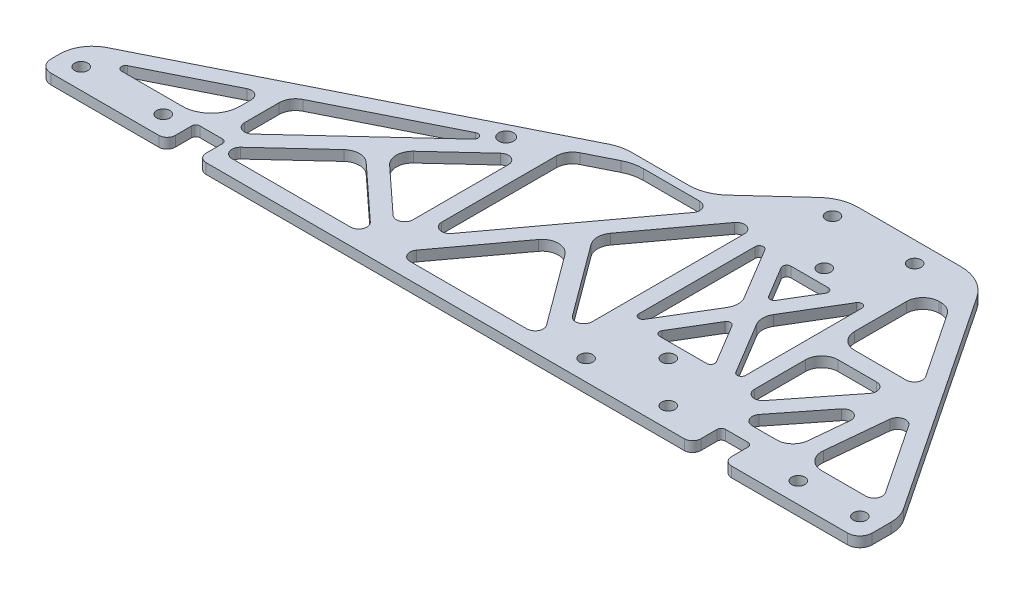
SolidWorks part; units mm, degrees
ref_plane "Front Plane" through (0, 0, 0) normal (0, 0, 1) x (1, 0, 0)
ref_plane "Top Plane" through (0, 0, 0) normal (0, 1, 0) x (1, 0, 0)
ref_plane "Right Plane" through (0, 0, 0) normal (1, 0, 0) x (0, 0, -1)
sketch "Sketch1" plane through (0, 0, 0) normal (0, 1, 0) x (1, 0, 0)
  line L0 (0, 0) -> (254, 0)
  line L2 (203.2, 88.9) -> (152.4, 88.9)
  line L4 (0, 0) -> (0, 12.7)
  line L5 (0, 12.7) -> (152.4, 88.9)
  line L6 (203.2, 88.9) -> (254, 12.7)
  line L7 (254, 12.7) -> (254, 0)
  line L8 (0, 6.35) -> (44.45, 6.35) construction
  line L9 (254, 6.35) -> (228.6, 6.35) construction
  line L10 (139.7, 82.55) -> (207.4333, 82.55) construction
  line L11 (44.45, 0) -> (44.45, 34.925) construction
  line L12 (156.6333, 12.7) -> (154.0933, 7.62)
  line L13 (224.7006, 47.4909) -> (221.314, 12.7) construction
  line L20 (127, 76.2) -> (211.6667, 76.2)
  line L21 (154.0933, 76.2) -> (101.6, 5.08) construction
  line L22 (154.0933, 12.7) -> (154.0933, 7.62)
  line L23 (247.8946, 12.7) -> (194.7333, 12.7)
  line L24 (224.7006, 47.4909) -> (197.2733, 12.7) construction
  line L28 (224.7006, 47.4909) -> (194.7333, 47.4909) construction
  line L31 (5.08, 9.5604) -> (153.5992, 83.82)
  line L32 (200.4813, 83.82) -> (153.5992, 83.82)
  line L33 (200.4813, 83.82) -> (248.92, 11.1619)
  line L34 (248.92, 11.1619) -> (248.92, 5.08)
  line L35 (5.08, 5.08) -> (248.92, 5.08)
  line L36 (5.08, 5.08) -> (5.08, 9.5604)
  line L37 (101.6, 5.08) -> (101.6, 57.8204) construction
  line L39 (127.8467, 40.64) -> (154.0933, 5.08) construction
  line L40 (101.6, 57.8204) -> (44.45, 5.08) construction
  line L41 (73.025, 31.4502) -> (101.6, 5.08) construction
  line L42 (154.0933, 7.62) -> (154.0933, 5.08)
  line L83 (152.8233, 5.08) -> (150.2833, 0)
  line L84 (125.803, 39.1316) -> (152.0497, 3.5716)
  line L107 (152.0497, 77.7084) -> (99.5564, 6.5884)
  line L108 (156.6333, 76.2) -> (194.7333, 12.7) construction
  line L113 (194.7333, 76.2) -> (156.6333, 12.7) construction
  line L117 (104.14, 5.08) -> (104.14, 63.6207)
  line L118 (156.6333, 12.7) -> (194.7333, 12.7)
  line L119 (194.7333, 12.7) -> (201.0833, 0)
  line L120 (154.0933, 6.35) -> (197.9083, 6.35) construction
  line L126 (192.5553, 77.5068) -> (154.4553, 14.0068)
  line L127 (154.4553, 74.8932) -> (192.5553, 11.3932)
  line L128 (156.6333, 12.7) -> (156.6333, 76.2) construction
  line L129 (194.7333, 12.7) -> (194.7333, 76.2) construction
  line L130 (197.2733, 12.7) -> (197.2733, 76.2)
  line L131 (159.1733, 12.7) -> (159.1733, 76.2)
  line L132 (192.1933, 12.7) -> (192.1933, 76.2)
  line L133 (154.0933, 12.7) -> (154.0933, 76.2)
  line L147 (196.9114, 74.8932) -> (158.8114, 11.3932)
  line L148 (158.8114, 77.5068) -> (196.9114, 14.0068)
  line L154 (104.14, 63.6207) -> (42.7274, 6.9466)
  line L155 (71.3024, 29.5836) -> (99.8774, 3.2134)
  line L156 (224.7006, 50.0309) -> (194.7333, 50.0309)
  line L157 (222.7059, 49.0635) -> (195.2786, 14.2725)
  line L158 (197.2733, 12.7) -> (197.2733, 7.62)
  line L159 (222.1726, 47.737) -> (218.7859, 12.9461)
  line L160 (129.8903, 42.1484) -> (156.137, 6.5884)
  line L163 (156.137, 74.6916) -> (103.6436, 3.5716)
  line L164 (99.06, 5.08) -> (99.06, 52.0201)
  line L165 (99.06, 52.0201) -> (46.1726, 3.2134)
  line L166 (175.6833, 19.05) -> (162.9833, 6.35) construction
  line L167 (175.6833, 19.05) -> (188.3833, 6.35) construction
  line L168 (162.9833, 82.55) -> (175.6833, 67.31) construction
  line L169 (175.6833, 67.31) -> (188.3833, 82.55) construction
  line L170 (161.6625, 21.082) -> (189.7041, 21.082) construction
  line L171 (161.6625, 23.622) -> (189.7041, 23.622)
  line L172 (163.1865, 65.278) -> (188.1801, 65.278) construction
  line L173 (163.1865, 62.738) -> (188.1801, 62.738)
  line L174 (74.7476, 33.3168) -> (103.3226, 6.9466)
  line L175 (224.7006, 44.9509) -> (194.7333, 44.9509)
  line L176 (226.6953, 45.9184) -> (199.268, 11.1275)
  line L177 (227.2287, 47.2449) -> (223.842, 12.4539)
  line L178 (8.8192, 11.43) -> (44.45, 11.43)
  line L179 (46.99, 0) -> (46.99, 34.925)
  line L180 (41.91, 0) -> (41.91, 34.925)
  line L181 (198.2745, 13.97) -> (221.4376, 13.97)
  line L182 (118.0392, 66.04) -> (146.5943, 66.04)
  circle A0 centre (6.7733, 6.35) radius 2.032
  circle A1 centre (32.1733, 6.35) radius 2.032
  circle A2 centre (228.6, 6.35) radius 2.032
  circle A3 centre (247.65, 6.35) radius 2.032
  circle A4 centre (162.9833, 82.55) radius 2.032
  circle A5 centre (188.3833, 82.55) radius 2.032
  circle A28 centre (162.9833, 6.35) radius 2.032
  circle A29 centre (188.3833, 6.35) radius 2.032
  arc A32 (197.2733, 12.7) -> (192.1933, 12.7) centre (194.7333, 12.7) cw
  arc A33 (197.2733, 76.2) -> (192.1933, 76.2) centre (194.7333, 76.2) ccw
  arc A34 (159.1733, 12.7) -> (154.0933, 12.7) centre (156.6333, 12.7) cw
  arc A35 (159.1733, 76.2) -> (154.0933, 76.2) centre (156.6333, 76.2) ccw
  arc A45 (192.5553, 77.5068) -> (196.9114, 74.8932) centre (194.7333, 76.2) cw
  arc A46 (154.4553, 14.0068) -> (158.8114, 11.3932) centre (156.6333, 12.7) ccw
  arc A47 (154.4553, 74.8932) -> (158.8114, 77.5068) centre (156.6333, 76.2) cw
  arc A48 (192.5553, 11.3932) -> (196.9114, 14.0068) centre (194.7333, 12.7) ccw
  circle A59 centre (175.6833, 19.05) radius 2.032
  circle A60 centre (175.6833, 67.31) radius 2.032
  arc A61 (125.803, 39.1316) -> (129.8903, 42.1484) centre (127.8467, 40.64) cw
  arc A62 (152.0497, 3.5716) -> (156.137, 6.5884) centre (154.0933, 5.08) ccw
  arc A63 (152.0497, 77.7084) -> (156.137, 74.6916) centre (154.0933, 76.2) cw
  arc A64 (99.5564, 6.5884) -> (103.6436, 3.5716) centre (101.6, 5.08) ccw
  arc A65 (104.14, 5.08) -> (99.06, 5.08) centre (101.6, 5.08) cw
  arc A66 (42.7274, 6.9466) -> (46.1726, 3.2134) centre (44.45, 5.08) ccw
  arc A67 (71.3024, 29.5836) -> (74.7476, 33.3168) centre (73.025, 31.4502) cw
  arc A68 (99.8774, 3.2134) -> (103.3226, 6.9466) centre (101.6, 5.08) ccw
  arc A69 (224.7006, 50.0309) -> (224.7006, 44.9509) centre (224.7006, 47.4909) cw
  arc A70 (194.7333, 50.0309) -> (194.7333, 44.9509) centre (194.7333, 47.4909) ccw
  arc A71 (222.7059, 49.0635) -> (226.6953, 45.9184) centre (224.7006, 47.4909) cw
  arc A72 (195.2786, 14.2725) -> (199.268, 11.1275) centre (197.2733, 12.7) ccw
  arc A73 (222.1726, 47.737) -> (227.2287, 47.2449) centre (224.7006, 47.4909) cw
  arc A74 (218.7859, 12.9461) -> (223.842, 12.4539) centre (221.314, 12.7) ccw
  arc A75 (46.99, 0) -> (41.91, 0) centre (44.45, 0) cw
  arc A76 (46.99, 34.925) -> (41.91, 34.925) centre (44.45, 34.925) ccw
  dimension "D7" = 4.064
  dimension "D8" = 25.4
  dimension "D9" = 130.81
  dimension "D10" = 19.05
  dimension "D11" = 6.35
  dimension "D13" = 19.05
  dimension "D1" = 254
  dimension "D2" = 50.8
  dimension "D3" = 88.9
  dimension "D4" = 152.4
  dimension "D5" = 12.7
  dimension "D6" = 6.35
  dimension "D12" = 25.4
  dimension "D14" = 44.45
  dimension "D15" = 12.7
  dimension "D16" = 57.15
  dimension "D18" = 12.7
  dimension "D19" = 2.54
  dimension "D20" = 50.8
  dimension "D21" = 25.4
  dimension "D22" = 2.54
  dimension "D23" = 6.35
  dimension "D24" = 2.54
  dimension "D29" = 6.35
  dimension "D30" = 38.1
  dimension "D31" = 25.4
  dimension "D32" = 6.35
  dimension "D33" = 2.54
  dimension "D36" = 12.7
  dimension "D38" = 15.24
  dimension "D39" = 2.54
  dimension "D40" = 2.54
  dimension "D27" = 1.27
  dimension "D28" = 17.78
  dimension "D17" = 5.08
  dimension "D25" = 2.54
  dimension "D26" = 2.54
  dimension "D37" = 2.54
extrude "Boss-Extrude1" add sketch "Sketch1" along normal blind 3.175 contours L0 L7 L6 L2 L5 L4 | A0 | A1 | A5 | A4 | A2 | A3
extrude "Cut-Extrude2" cut sketch "Sketch1<3>" along normal through all contours L154 L31 L11 | L155 L165 L35 | L165 L174 L164 | L117 L107 L20 L31 | L84 L163 L35 | L133 L163 L160 L22 | L157 L175 L130 | L156 L33 L20 L130 | L147 L148 L132 | L131 L126 L127 | L173 L148 L126 | L147 L171 L127 | L33 L177 L23 | L178 L180 L31 | L176 L181 L159 | A28 | A59 | A29 | A60 region at (30.8797, 0, -16.9451) region at (73.025, 0, -12.718) region at (62.4687, 0, -31.7097) region at (127.8467, 0, -15.5076) region at (91.6301, 0, -31.4502) region at (117.6489, 0, -47.5459) region at (206.5243, 0, -60.8789) region at (146.3968, 0, -40.64) region at (204.6702, 0, -35.5682) region at (175.6833, 0, -28.919) region at (187.6774, 0, -44.45) region at (213.9093, 0, -22.3524) region at (163.6893, 0, -44.45) region at (232.896, 0, -23.1836) region at (175.6833, 0, -58.2876)
sketch "Sketch1<3>" plane through (0, 0, 0) normal (0, 1, 0) x (1, 0, 0) same geometry as "Sketch1"
fillet "Fillet1" radius 3.81 2 edges at (254, 1.5875, 0) (0, 1.5875, 0)
fillet "Fillet2" radius 10.16 2 edges at (254, 1.5875, -12.7) (0, 1.5875, -12.7)
fillet "Fillet3" radius 12.7 2 edges at (203.2, 1.5875, -88.9) (152.4, 1.5875, -88.9)
fillet "Fillet4" radius 1.27 12 edges at (159.1733, 1.5875, -67.0298) (192.1933, 1.5875, -67.0298) (192.1933, 1.5875, -21.8702) (159.1733, 1.5875, -21.8702) (183.694, 1.5875, -62.738) (167.6727, 1.5875, -62.738) (175.6833, 1.5875, -49.3869) (185.218, 1.5875, -23.622) (166.1487, 1.5875, -23.622) (175.6833, 1.5875, -39.5131) (93.426, 1.5875, -53.7334) (8.8192, 1.5875, -11.43)
fillet "Fillet5" radius 2.54 19 edges at (223.0073, 1.5875, -50.0309) (247.8946, 1.5875, -12.7) (226.9275, 1.5875, -44.1507) (221.3335, 1.5875, -39.1171) (197.2733, 1.5875, -16.8027) (219.4639, 1.5875, -44.9509) (104.14, 1.5875, -12.7984) (99.06, 1.5875, -52.0201) (48.1953, 1.5875, -5.08) (97.8547, 1.5875, -5.08) (99.06, 1.5875, -10.8803) (104.7569, 1.5875, -5.08) (150.9364, 1.5875, -5.08) (154.0933, 1.5875, -9.3572) (154.0933, 1.5875, -71.9228) (41.91, 1.5875, -27.9754) (46.99, 1.5875, -10.8803) (201.5089, 1.5875, -13.97) (143.4373, 1.5875, -66.04)
fillet "Fillet6" radius 5.08 14 edges at (172.7212, 1.5875, -44.45) (178.6455, 1.5875, -44.45) (223.866, 1.5875, -12.7) (197.2733, 1.5875, -50.0309) (197.2733, 1.5875, -44.9509) (197.2733, 1.5875, -76.2) (205.5613, 1.5875, -76.2) (73.025, 1.5875, -27.9939) (76.7703, 1.5875, -31.4502) (104.14, 1.5875, -59.0904) (131.0036, 1.5875, -40.64) (127.8467, 1.5875, -36.3628) (46.99, 1.5875, -30.5154) (218.8856, 1.5875, -13.97)
fillet "Fillet7" radius 12.7 1 edges at (118.0392, 1.5875, -66.04)
fillet "Fillet10" radius 8.89 1 edges at (41.91, 1.5875, -11.43)
sketch "Sketch4" plane through (0, 3.175, 0) normal (0, 1, 0) x (1, 0, 0)
  line L0 (121.0373, 66.04) -> (138.4056, 66.04) construction
  line L1 (121.0373, 66.04) -> (138.4056, 66.04)
  line L2 (121.0373, 68.58) -> (113.3689, 68.58) construction
  line L4 (138.4056, 66.04) -> (163.3832, 88.9)
  line L5 (121.0373, 68.58) -> (111.76, 68.58)
  line L6 (252.2936, 15.2596) -> (206.9702, 83.2447)
  line L7 (196.4032, 88.9) -> (155.3981, 88.9)
  line L8 (149.7185, 87.5592) -> (5.6163, 15.5082)
  line L9 (0, 6.4208) -> (0, 3.81)
  line L10 (3.81, 0) -> (250.19, 0)
  line L11 (254, 3.81) -> (254, 9.6238)
  line L12 (252.2936, 15.2596) -> (206.9702, 83.2447)
  line L13 (196.4032, 88.9) -> (155.3981, 88.9)
  line L14 (149.7185, 87.5592) -> (5.6163, 15.5082)
  line L15 (0, 6.4208) -> (0, 3.81)
  line L16 (3.81, 0) -> (250.19, 0)
  line L17 (254, 3.81) -> (254, 9.6238)
  line L18 (121.0373, 68.58) -> (137.4188, 68.58)
  line L19 (137.4188, 68.58) -> (159.621, 88.9)
  line L20 (138.4056, 66.04) -> (155.3658, 81.5624) construction
  line L21 (196.4032, 88.9) -> (155.3981, 88.9) construction
  line L22 (137.4188, 68.58) -> (153.651, 83.4361) construction
  line L23 (5.6163, 15.5082) -> (149.7185, 87.5592) construction
  line L29 (121.0373, 66.04) -> (113.3689, 66.04) construction
  arc A6 (206.9702, 83.2447) -> (196.4032, 88.9) centre (196.4032, 76.2) ccw
  arc A7 (155.3981, 88.9) -> (149.7185, 87.5592) centre (155.3981, 76.2) ccw
  arc A8 (5.6163, 15.5082) -> (0, 6.4208) centre (10.16, 6.4208) ccw
  arc A9 (0, 3.81) -> (3.81, 0) centre (3.81, 3.81) ccw
  arc A10 (250.19, 0) -> (254, 3.81) centre (250.19, 3.81) ccw
  arc A11 (254, 9.6238) -> (252.2936, 15.2596) centre (243.84, 9.6238) ccw
  arc A12 (206.9702, 83.2447) -> (196.4032, 88.9) centre (196.4032, 76.2) ccw
  arc A13 (155.3981, 88.9) -> (149.7185, 87.5592) centre (155.3981, 76.2) ccw
  arc A14 (5.6163, 15.5082) -> (0, 6.4208) centre (10.16, 6.4208) ccw
  arc A15 (0, 3.81) -> (3.81, 0) centre (3.81, 3.81) ccw
  arc A16 (250.19, 0) -> (254, 3.81) centre (250.19, 3.81) ccw
  arc A17 (254, 9.6238) -> (252.2936, 15.2596) centre (243.84, 9.6238) ccw
  point P18 (111.76, 68.58)
  point P28 (163.223, 94.3115)
  point P30 (164.7518, 88.9)
  point P33 (159.7969, 88.9)
  dimension "D2" = 2.54
  dimension "D4" = 33.02
  dimension "D1" = 0
extrude "Cut-Extrude5" cut sketch "Sketch4" against normal through all and the other way through all contours L13 A13 L14 L5 L18 L19 region at (137.3323, 3.175, -76.8167)
fillet "Fillet11" radius 12.7 3 edges at (111.76, 1.5875, -68.58) (159.621, 1.5875, -88.9) (137.4188, 1.5875, -68.58)
sketch "Sketch2" plane through (0, 3.175, 0) normal (0, 1, 0) x (1, 0, 0)
  line L0 (39.6875, 0) -> (39.6875, 8.89)
  line L1 (3.81, 0) -> (250.19, 0) construction
  line L2 (39.6875, 8.89) -> (49.2125, 8.89)
  line L3 (49.2125, 8.89) -> (49.2125, 0)
  line L4 (0, 3.81) -> (0, 6.4208) construction
  line L5 (202.2475, 0) -> (202.2475, 8.89)
  line L6 (202.2475, 8.89) -> (211.7725, 8.89)
  line L7 (211.7725, 8.89) -> (211.7725, 0)
  line L8 (254, 9.6238) -> (254, 3.81) construction
  line L9 (3.81, 0) -> (250.19, 0)
  dimension "D1" = 39.6875
  dimension "D2" = 9.525
  dimension "D3" = 8.89
  dimension "D4" = 42.2275
extrude "Cut-Extrude3" cut sketch "Sketch2" against normal through all contours L0 L9 L3 L2 | L5 L9 L7 L6 region at (207.01, 3.175, -4.445) region at (44.45, 3.175, -4.445)
fillet "Fillet8" radius 1.27 4 edges at (211.7725, 1.5875, -8.89) (202.2475, 1.5875, -8.89) (49.2125, 1.5875, -8.89) (39.6875, 1.5875, -8.89)
fillet "Fillet9" radius 2.54 4 edges at (49.2125, 1.5875, 0) (39.6875, 1.5875, 0) (211.7725, 1.5875, 0) (202.2475, 1.5875, 0)
sketch "Sketch3" plane through (0, 3.175, 0) normal (0, 1, 0) x (1, 0, 0)
  line L0 (322.9659, 17.0563) -> (94.1827, 68.4886) construction
  circle A0 centre (322.9659, 17.0563) radius 2.286 construction
  circle A1 centre (322.9659, 17.0563) radius 2.286
  circle A2 centre (91.2882, 53.2846) radius 2.286
  arc A4 (94.1827, 68.4886) -> (88.6111, 9.0045) centre (322.9659, 17.0563) ccw construction
  dimension "D1" = 234.4931
  dimension "D2" = 4.572
extrude "Cut-Extrude4" cut sketch "Sketch3" against normal up to surface (3.175 mm away) contours A2 region at (91.2882, 3.175, -53.2846) up to face at (233.1564, 0, -22.5815)
